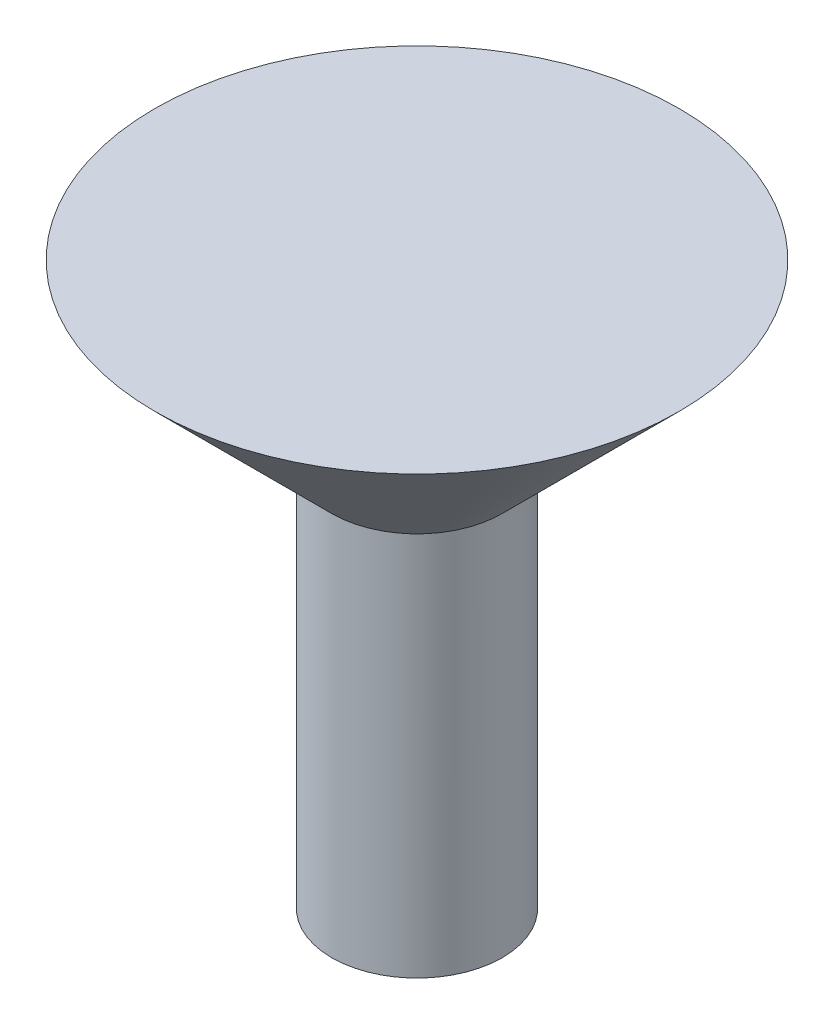
SolidWorks part; units mm, degrees
ref_plane "Front Plane" through (0, 0, 0) normal (0, 0, 1) x (1, 0, 0)
ref_plane "Top Plane" through (0, 0, 0) normal (0, 1, 0) x (1, 0, 0)
ref_plane "Right Plane" through (0, 0, 0) normal (1, 0, 0) x (0, 0, -1)
sketch "Sketch1" plane through (0, 0, 0) normal (0, 0, 1) x (1, 0, 0)
  line L0 (0, 2.5) -> (0, -2.5) construction
  line L1 (0, -2.5) -> (-2.5, -2.5) construction
  line L2 (-2.5, -2.5) -> (-7.5, 2.5) construction
  line L3 (-7.5, 2.5) -> (0, 2.5) construction
  line L4 (-0.2, 2.3) -> (-0.2, -2.3)
  line L5 (-0.2, -2.3) -> (-2.4172, -2.3)
  line L6 (-2.4172, -2.3) -> (-7.0172, 2.3)
  line L7 (-7.0172, 2.3) -> (-0.2, 2.3)
  dimension "D1" = 5
  dimension "D2" = 7.5
  dimension "D3" = 2.5
  dimension "D4" = 0.2
revolve "Revolve1" add sketch "Sketch1" angle 360 about L4
sketch "Sketch2" plane through (0, -2.3, 0) normal (0, -1, 0) x (1, 0, 0)
  circle A1 centre (-0.2, 0) radius 2.2172
  circle A2 centre (-0.2, 0) radius 2.2172
  dimension "D1" = 0
extrude "Boss-Extrude1" add sketch "Sketch2" along normal blind 10
sketch "Sketch3" plane through (0, -12.3, 0) normal (0, -1, 0) x (1, 0, 0)
  circle A0 centre (-0.2, 0) radius 1.05
  circle A1 centre (-0.2, 0) radius 2.2172 construction
  dimension "D1" = 2.1
extrude "Boss-Extrude2" add sketch "Sketch3" against normal blind 3
extrude "Cut-Extrude1" cut sketch "Sketch3<2>" against normal blind 6
sketch "Sketch3<2>" plane through (0, -12.3, 0) normal (0, -1, 0) x (1, 0, 0) same geometry as "Sketch3"
fillet "Fillet1" radius 1 1 edges at (-0.2, -6.3, -1.05)
chamfer "Chamfer1" distance 0.5 angle 45 1 edges at (-0.2, -12.3, -1.05)
